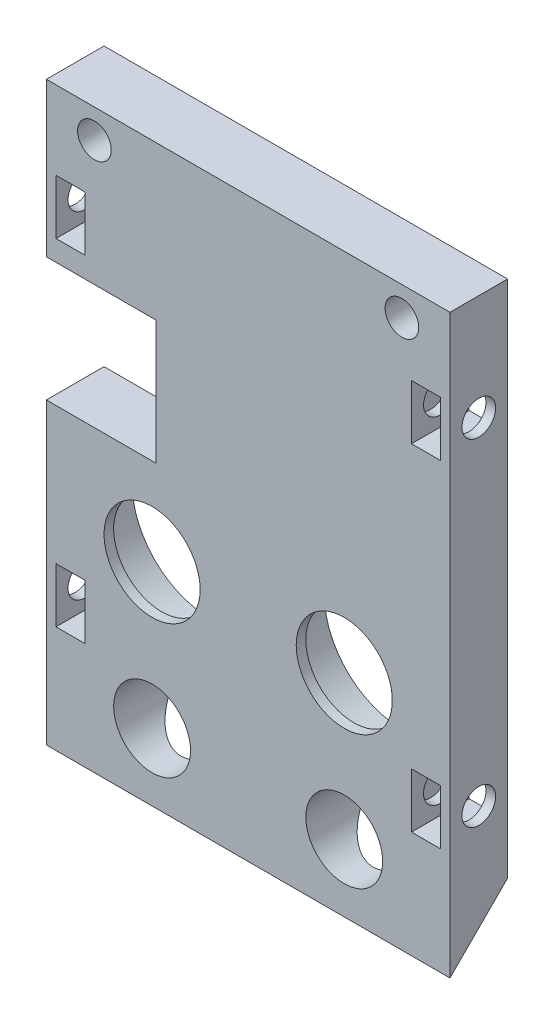
SolidWorks part; units mm, degrees
ref_plane "Front Plane" through (0, 0, 0) normal (0, 0, 1) x (1, 0, 0)
ref_plane "Top Plane" through (0, 0, 0) normal (0, 1, 0) x (1, 0, 0)
ref_plane "Right Plane" through (0, 0, 0) normal (1, 0, 0) x (0, 0, -1)
sketch "Sketch1" plane through (0, 0, 0) normal (0, 0, 1) x (1, 0, 0)
  line L0 (-21, -23) -> (21, -23) construction
  line L1 (-21, -30) -> (21, -30)
  line L2 (-21, 30) -> (-21, -8)
  line L3 (-21, 30) -> (21, 30)
  line L4 (21, -30) -> (21, 30)
  line L5 (-21, -30) -> (21, 30) construction
  line L6 (-21, 30) -> (21, -30) construction
  line L7 (-21, -8) -> (21, -8) construction
  line L8 (0, 0) -> (0, 14.9714) construction
  line L9 (21, 27) -> (-21, 27) construction
  line L13 (-21, -8) -> (-21, -30)
  circle A0 centre (-10, -23) radius 4
  circle A1 centre (-10, -8) radius 5
  circle A2 centre (10, -8) radius 5
  circle A3 centre (10, -23) radius 4
  circle A4 centre (16, 27) radius 1.75
  circle A5 centre (-16, 27) radius 1.75
  point P0 (0, 0)
  point P21 (0, -8)
  dimension "D1" = 10
  dimension "D2" = 8
  dimension "D10" = 5
  dimension "D9" = 3.5
  dimension "D3" = 3
  dimension "D4" = 15
  dimension "D5" = 0
  dimension "D6" = 38
  dimension "D7" = 7
  dimension "D8" = 10
  dimension "D14" = 10
extrude "Boss-Extrude1" add sketch "Sketch1" along normal blind 6
sketch "Sketch2" plane through (0, 0, 6) normal (0, 0, 1) x (1, 0, 0)
  line L0 (0, 30) -> (0, 8.6133) construction
  line L1 (21, 30) -> (-21, 30) construction
  circle A0 centre (-10, -8) radius 8.075
  circle A1 centre (10, -8) radius 8.075
  dimension "D1" = 16.15
chamfer "Chamfer1" distance 6 angle 45 1 edges at (0, -30, 0)
sketch "Sketch3" plane through (0, 0, 0) normal (0, 0, -1) x (-1, 0, 0)
  line L1 (21, 30) -> (21, -30) construction
  line L5 (-21, 30) -> (21, 30) construction
  line L6 (0, 30) -> (0, 20.9596) construction
  line L7 (9.6, 14) -> (9.6116, 1.1)
  line L8 (21, 1.1) -> (9.6116, 1.1)
  line L9 (21, 14) -> (21, 1.1)
  line L10 (21, 14) -> (9.6, 14)
  dimension "D1" = 12.9
  dimension "D2" = 11.4
  dimension "D3" = 16
extrude "Cut-Extrude2" cut sketch "Sketch3" against normal blind 10
sketch "Sketch4" plane through (0, 0, 0) normal (0, 0, -1) x (-1, 0, 0)
  line L0 (-21, -24) -> (-21, -18.85) construction
  line L1 (-20, -13.15) -> (-17, -13.15)
  line L2 (-20, -13.15) -> (-20, -18.85)
  line L3 (-20, -18.85) -> (-17, -18.85)
  line L4 (-17, -13.15) -> (-17, -18.85)
  line L5 (-20, -13.15) -> (-17, -18.85) construction
  line L6 (-20, -18.85) -> (-17, -13.15) construction
  line L8 (20, -18.85) -> (17, -13.15) construction
  line L9 (20, -13.15) -> (17, -18.85) construction
  line L10 (21, -24) -> (21, -18.85) construction
  line L11 (17, -13.15) -> (17, -18.85)
  line L12 (20, -18.85) -> (17, -18.85)
  line L13 (20, -13.15) -> (20, -18.85)
  line L14 (-21, -24) -> (-21, 30) construction
  line L15 (-20, 21.85) -> (-17, 21.85)
  line L16 (-20, 21.85) -> (-20, 16.15)
  line L17 (-20, 16.15) -> (-17, 16.15)
  line L18 (-17, 21.85) -> (-17, 16.15)
  line L19 (17, 21.85) -> (17, 16.15)
  line L20 (20, 16.15) -> (17, 16.15)
  line L21 (21, -30) -> (-21, -30) construction
  line L22 (0, 0) -> (0, -7.2757) construction
  line L23 (20, -13.15) -> (17, -13.15)
  line L24 (20, 21.85) -> (20, 16.15)
  line L25 (20, 21.85) -> (17, 21.85)
  line L26 (-21, 11) -> (-21, 16.15) construction
  line L27 (-20, 21.85) -> (-17, 16.15) construction
  line L28 (-20, 16.15) -> (-17, 21.85) construction
  line L29 (20, 16.15) -> (17, 21.85) construction
  line L30 (20, 21.85) -> (17, 16.15) construction
  line L31 (21, 11) -> (21, 16.15) construction
  point P0 (-18.5, -16)
  point P21 (-18.5, 19)
  point P24 (18.5, -16)
  point P37 (18.5, 19)
  dimension "D1" = 3
  dimension "D2" = 5.7
  dimension "D3" = 14
  dimension "D4" = 1
  dimension "D5" = 2
extrude "Cut-Extrude3" cut sketch "Sketch4" against normal through all contours L4 L1 L2 L3 | L13 L23 L11 L12 | L18 L15 L16 L17 | L24 L25 L19 L20 region at (18.5, -16, 0) region at (-18.5, -16, 0) region at (18.5, 19, 0) region at (-18.5, 19, 0)
extrude "Cut-Extrude4" cut sketch "Sketch2" along normal blind 5 from offset 6 offset against normal yes
sketch "Sketch5" plane through (21, 0, 0) normal (1, 0, 0) x (0, 0, -1)
  line L0 (-3, 30) -> (-3, -27) construction
  line L1 (-6, 30) -> (0, 30) construction
  line L2 (-6, -30) -> (0, -24) construction
  circle A0 centre (-3, -16) radius 1.75
  circle A1 centre (-3, 19) radius 1.75
  dimension "D1" = 3.5
  dimension "D2" = 3.5
  dimension "D3" = 14
  dimension "D4" = 35
extrude "Cut-Extrude5" cut sketch "Sketch5" against normal blind 5
mirror "Mirror1" about plane through (0, 0, 0) normal (1, 0, 0) of "Cut-Extrude5"
